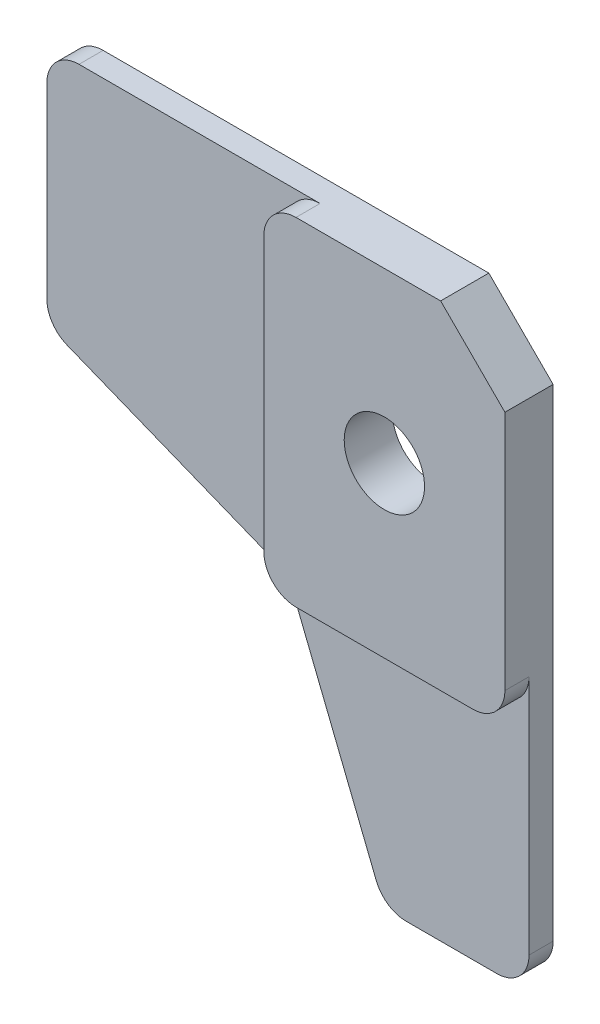
SolidWorks part; units mm, degrees
ref_plane "Front Plane" through (0, 0, 0) normal (0, 0, 1) x (1, 0, 0)
ref_plane "Top Plane" through (0, 0, 0) normal (0, 1, 0) x (1, 0, 0)
ref_plane "Right Plane" through (0, 0, 0) normal (1, 0, 0) x (0, 0, -1)
sketch "Sketch1" plane through (0, 0, 0) normal (0, 0, 1) x (1, 0, 0)
  line L0 (11, 21) -> (15, 17)
  line L1 (0, 0) -> (15, 0)
  line L2 (0, 0) -> (0, 21)
  line L3 (0, 21) -> (11, 21)
  line L4 (15, 0) -> (15, 17)
  dimension "D1" = 21
  dimension "D2" = 15
  dimension "D3" = 4
  dimension "D4" = 4
extrude "Boss-Extrude1" add sketch "Sketch1" along normal blind 1.5
sketch "Sketch2" plane through (0, 0, 0) normal (0, 0, -1) x (-1, 0, 0)
  line L0 (0, 0) -> (15, 6)
  line L1 (0, 21) -> (15, 21)
  line L4 (15, 21) -> (15, 6)
  line L5 (0, 0) -> (0, 21)
  line L6 (0, 21) -> (-11, 21)
  line L7 (-11, 21) -> (-15, 17)
  line L8 (-15, 17) -> (-15, 0)
  line L9 (-15, 0) -> (0, 0)
  line L11 (0, 21) -> (-11, 21)
  line L12 (-11, 21) -> (-15, 17)
  line L13 (-15, 17) -> (-15, 0)
  line L16 (-15, 0) -> (-15, -15)
  line L17 (-15, -15) -> (-6, -15)
  line L19 (0, 0) -> (-6, -15)
  dimension "D2" = 15
  dimension "D3" = 9
  dimension "D4" = 15
  dimension "D5" = 15
  dimension "D1" = 0
extrude "Boss-Extrude2" add sketch "Sketch2" along normal blind 1.5
fillet "Fillet1" radius 2 7 edges at (15, -15, -0.75) (6, -15, -0.75) (-15, 21, -0.75) (-15, 6, -0.75) (0, 21, 0.75) (15, 0, 0.75) (0, 0, 0.75)
sketch "Sketch3" plane through (0, 0, -1.5) normal (0, 0, -1) x (-1, 0, 0)
  line L7 (-15, 17) -> (-15, -13)
  line L8 (-13, -15) -> (-7.3541, -15)
  line L9 (-5.4971, -13.7428) -> (0, 0)
  line L10 (0, 0) -> (13.7428, 5.4971)
  line L11 (15, 7.3541) -> (15, 19)
  line L12 (13, 21) -> (-11, 21)
  line L13 (-11, 21) -> (-15, 17)
  line L14 (-15, 17) -> (-15, -13)
  line L15 (-13, -15) -> (-7.3541, -15)
  line L16 (-5.4971, -13.7428) -> (0, 0)
  line L17 (0, 0) -> (13.7428, 5.4971)
  line L18 (15, 7.3541) -> (15, 19)
  line L19 (13, 21) -> (-11, 21)
  line L20 (-11, 21) -> (-15, 17)
  circle A0 centre (-7.5, 10.5) radius 2.5
  arc A4 (-15, -13) -> (-13, -15) centre (-13, -13) ccw
  arc A5 (-7.3541, -15) -> (-5.4971, -13.7428) centre (-7.3541, -13) ccw
  arc A6 (13.7428, 5.4971) -> (15, 7.3541) centre (13, 7.3541) ccw
  arc A7 (15, 19) -> (13, 21) centre (13, 19) ccw
  arc A8 (-15, -13) -> (-13, -15) centre (-13, -13) ccw
  arc A9 (-7.3541, -15) -> (-5.4971, -13.7428) centre (-7.3541, -13) ccw
  arc A10 (13.7428, 5.4971) -> (15, 7.3541) centre (13, 7.3541) ccw
  arc A11 (15, 19) -> (13, 21) centre (13, 19) ccw
  dimension "D2" = 5
  dimension "D3" = 10.5
  dimension "D4" = 7.5
  dimension "D1" = 0
extrude "Cut-Extrude1" cut sketch "Sketch3" against normal through all flip side to cut
ref_plane "Plane1" [suppressed] through (0, 0, 11.5) normal (0, 0, 1) x (1, 0, 0)
mirror "Mirror4" [suppressed] about plane through (0, 0, 11.5) normal (0, 0, 1) of bodies 103
